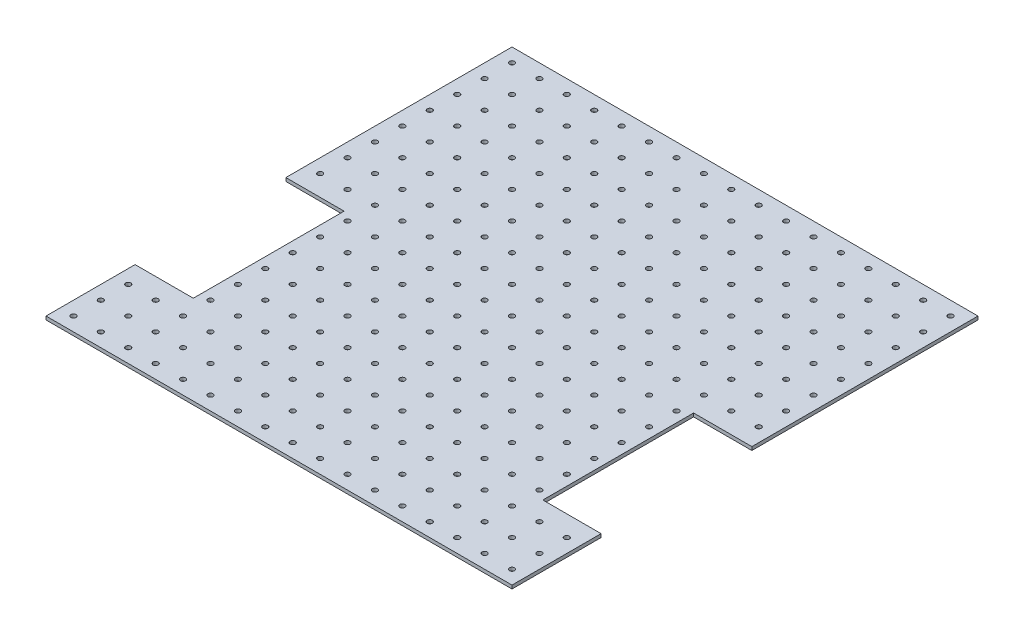
SolidWorks part; units mm, degrees
material "ABS"
ref_plane "Front Plane" through (0, 0, 0) normal (0, 0, 1) x (1, 0, 0)
ref_plane "Top Plane" through (0, 0, 0) normal (0, 1, 0) x (1, 0, 0)
ref_plane "Right Plane" through (0, 0, 0) normal (1, 0, 0) x (0, 0, -1)
sketch "Sketch1" plane through (0, 0, 0) normal (0, 1, 0) x (1, 0, 0)
  line L1 (-215.9, -215.9) -> (215.9, -215.9)
  line L2 (-215.9, -215.9) -> (-215.9, 215.9)
  line L3 (-215.9, 215.9) -> (215.9, 215.9)
  line L4 (215.9, -215.9) -> (215.9, 215.9)
  line L5 (-215.9, -215.9) -> (215.9, 215.9) construction
  line L6 (-215.9, 215.9) -> (215.9, -215.9) construction
  point P0 (0, 0)
  dimension "D1" = 431.8
  dimension "D2" = 431.8
extrude "Boss-Extrude1" add sketch "Sketch1" along normal blind 3.175
sketch "Sketch2" plane through (0, 3.175, 0) normal (0, 1, 0) x (1, 0, 0)
  line L1 (-215.9, -215.9) -> (-203.2, -215.9) construction
  line L2 (-215.9, -215.9) -> (-215.9, -203.2) construction
  line L3 (-215.9, -203.2) -> (-203.2, -203.2) construction
  line L4 (-203.2, -215.9) -> (-203.2, -203.2) construction
  circle A0 centre (-203.2, -203.2) radius 2.3813
  circle A1 centre (-177.8, -203.2) radius 2.3813
  circle A2 centre (-152.4, -203.2) radius 2.3813
  circle A3 centre (-127, -203.2) radius 2.3813
  circle A4 centre (-101.6, -203.2) radius 2.3813
  circle A5 centre (-76.2, -203.2) radius 2.3813
  circle A6 centre (-50.8, -203.2) radius 2.3812
  circle A7 centre (-25.4, -203.2) radius 2.3813
  circle A8 centre (0, -203.2) radius 2.3813
  circle A9 centre (25.4, -203.2) radius 2.3812
  circle A10 centre (50.8, -203.2) radius 2.3812
  circle A11 centre (76.2, -203.2) radius 2.3813
  circle A12 centre (101.6, -203.2) radius 2.3813
  circle A13 centre (127, -203.2) radius 2.3813
  circle A14 centre (152.4, -203.2) radius 2.3813
  circle A15 centre (177.8, -203.2) radius 2.3813
  circle A16 centre (-177.8, -177.8) radius 2.3813
  circle A17 centre (-152.4, -177.8) radius 2.3813
  circle A18 centre (-127, -177.8) radius 2.3813
  circle A19 centre (-101.6, -177.8) radius 2.3813
  circle A20 centre (-76.2, -177.8) radius 2.3813
  circle A21 centre (-50.8, -177.8) radius 2.3812
  circle A22 centre (-25.4, -177.8) radius 2.3813
  circle A23 centre (0, -177.8) radius 2.3813
  circle A24 centre (25.4, -177.8) radius 2.3812
  circle A25 centre (50.8, -177.8) radius 2.3812
  circle A26 centre (76.2, -177.8) radius 2.3813
  circle A27 centre (101.6, -177.8) radius 2.3813
  circle A28 centre (127, -177.8) radius 2.3813
  circle A29 centre (152.4, -177.8) radius 2.3813
  circle A30 centre (177.8, -177.8) radius 2.3813
  circle A31 centre (-177.8, -152.4) radius 2.3813
  circle A32 centre (-152.4, -152.4) radius 2.3813
  circle A33 centre (-127, -152.4) radius 2.3813
  circle A34 centre (-101.6, -152.4) radius 2.3813
  circle A35 centre (-76.2, -152.4) radius 2.3813
  circle A36 centre (-50.8, -152.4) radius 2.3812
  circle A37 centre (-25.4, -152.4) radius 2.3813
  circle A38 centre (0, -152.4) radius 2.3813
  circle A39 centre (25.4, -152.4) radius 2.3813
  circle A40 centre (50.8, -152.4) radius 2.3813
  circle A41 centre (76.2, -152.4) radius 2.3813
  circle A42 centre (101.6, -152.4) radius 2.3813
  circle A43 centre (127, -152.4) radius 2.3813
  circle A44 centre (152.4, -152.4) radius 2.3813
  circle A45 centre (177.8, -152.4) radius 2.3813
  circle A46 centre (-177.8, -127) radius 2.3813
  circle A47 centre (-152.4, -127) radius 2.3813
  circle A48 centre (-127, -127) radius 2.3813
  circle A49 centre (-101.6, -127) radius 2.3813
  circle A50 centre (-76.2, -127) radius 2.3813
  circle A51 centre (-50.8, -127) radius 2.3812
  circle A52 centre (-25.4, -127) radius 2.3813
  circle A53 centre (0, -127) radius 2.3813
  circle A54 centre (25.4, -127) radius 2.3812
  circle A55 centre (50.8, -127) radius 2.3812
  circle A56 centre (76.2, -127) radius 2.3813
  circle A57 centre (101.6, -127) radius 2.3813
  circle A58 centre (127, -127) radius 2.3813
  circle A59 centre (152.4, -127) radius 2.3813
  circle A60 centre (177.8, -127) radius 2.3813
  circle A61 centre (-177.8, -101.6) radius 2.3813
  circle A62 centre (-152.4, -101.6) radius 2.3813
  circle A63 centre (-127, -101.6) radius 2.3813
  circle A64 centre (-101.6, -101.6) radius 2.3813
  circle A65 centre (-76.2, -101.6) radius 2.3813
  circle A66 centre (-50.8, -101.6) radius 2.3812
  circle A67 centre (-25.4, -101.6) radius 2.3813
  circle A68 centre (0, -101.6) radius 2.3813
  circle A69 centre (25.4, -101.6) radius 2.3812
  circle A70 centre (50.8, -101.6) radius 2.3812
  circle A71 centre (76.2, -101.6) radius 2.3813
  circle A72 centre (101.6, -101.6) radius 2.3813
  circle A73 centre (127, -101.6) radius 2.3813
  circle A74 centre (152.4, -101.6) radius 2.3813
  circle A75 centre (177.8, -101.6) radius 2.3813
  circle A76 centre (-177.8, -76.2) radius 2.3813
  circle A77 centre (-152.4, -76.2) radius 2.3813
  circle A78 centre (-127, -76.2) radius 2.3813
  circle A79 centre (-101.6, -76.2) radius 2.3813
  circle A80 centre (-76.2, -76.2) radius 2.3813
  circle A81 centre (-50.8, -76.2) radius 2.3812
  circle A82 centre (-25.4, -76.2) radius 2.3813
  circle A83 centre (0, -76.2) radius 2.3813
  circle A84 centre (25.4, -76.2) radius 2.3812
  circle A85 centre (50.8, -76.2) radius 2.3813
  circle A86 centre (76.2, -76.2) radius 2.3813
  circle A87 centre (101.6, -76.2) radius 2.3813
  circle A88 centre (127, -76.2) radius 2.3813
  circle A89 centre (152.4, -76.2) radius 2.3813
  circle A90 centre (177.8, -76.2) radius 2.3813
  circle A91 centre (-177.8, -50.8) radius 2.3813
  circle A92 centre (-152.4, -50.8) radius 2.3813
  circle A93 centre (-127, -50.8) radius 2.3813
  circle A94 centre (-101.6, -50.8) radius 2.3813
  circle A95 centre (-76.2, -50.8) radius 2.3813
  circle A96 centre (-50.8, -50.8) radius 2.3812
  circle A97 centre (-25.4, -50.8) radius 2.3813
  circle A98 centre (0, -50.8) radius 2.3813
  circle A99 centre (25.4, -50.8) radius 2.3812
  circle A100 centre (50.8, -50.8) radius 2.3813
  circle A101 centre (76.2, -50.8) radius 2.3813
  circle A102 centre (101.6, -50.8) radius 2.3813
  circle A103 centre (127, -50.8) radius 2.3813
  circle A104 centre (152.4, -50.8) radius 2.3813
  circle A105 centre (177.8, -50.8) radius 2.3813
  circle A106 centre (-177.8, -25.4) radius 2.3813
  circle A107 centre (-152.4, -25.4) radius 2.3813
  circle A108 centre (-127, -25.4) radius 2.3813
  circle A109 centre (-101.6, -25.4) radius 2.3813
  circle A110 centre (-76.2, -25.4) radius 2.3813
  circle A111 centre (-50.8, -25.4) radius 2.3812
  circle A112 centre (-25.4, -25.4) radius 2.3813
  circle A113 centre (0, -25.4) radius 2.3813
  circle A114 centre (25.4, -25.4) radius 2.3812
  circle A115 centre (50.8, -25.4) radius 2.3812
  circle A116 centre (76.2, -25.4) radius 2.3813
  circle A117 centre (101.6, -25.4) radius 2.3813
  circle A118 centre (127, -25.4) radius 2.3813
  circle A119 centre (152.4, -25.4) radius 2.3813
  circle A120 centre (177.8, -25.4) radius 2.3813
  circle A121 centre (-177.8, 0) radius 2.3813
  circle A122 centre (-152.4, 0) radius 2.3813
  circle A123 centre (-127, 0) radius 2.3813
  circle A124 centre (-101.6, 0) radius 2.3813
  circle A125 centre (-76.2, 0) radius 2.3813
  circle A126 centre (-50.8, 0) radius 2.3812
  circle A127 centre (-25.4, 0) radius 2.3813
  circle A128 centre (0, 0) radius 2.3813
  circle A129 centre (25.4, 0) radius 2.3812
  circle A130 centre (50.8, 0) radius 2.3812
  circle A131 centre (76.2, 0) radius 2.3813
  circle A132 centre (101.6, 0) radius 2.3813
  circle A133 centre (127, 0) radius 2.3813
  circle A134 centre (152.4, 0) radius 2.3813
  circle A135 centre (177.8, 0) radius 2.3813
  circle A136 centre (-177.8, 25.4) radius 2.3813
  circle A137 centre (-152.4, 25.4) radius 2.3813
  circle A138 centre (-127, 25.4) radius 2.3813
  circle A139 centre (-101.6, 25.4) radius 2.3813
  circle A140 centre (-76.2, 25.4) radius 2.3813
  circle A141 centre (-50.8, 25.4) radius 2.3812
  circle A142 centre (-25.4, 25.4) radius 2.3813
  circle A143 centre (0, 25.4) radius 2.3813
  circle A144 centre (25.4, 25.4) radius 2.3812
  circle A145 centre (50.8, 25.4) radius 2.3812
  circle A146 centre (76.2, 25.4) radius 2.3813
  circle A147 centre (101.6, 25.4) radius 2.3813
  circle A148 centre (127, 25.4) radius 2.3813
  circle A149 centre (152.4, 25.4) radius 2.3813
  circle A150 centre (177.8, 25.4) radius 2.3813
  circle A151 centre (-177.8, 50.8) radius 2.3813
  circle A152 centre (-152.4, 50.8) radius 2.3813
  circle A153 centre (-127, 50.8) radius 2.3813
  circle A154 centre (-101.6, 50.8) radius 2.3813
  circle A155 centre (-76.2, 50.8) radius 2.3813
  circle A156 centre (-50.8, 50.8) radius 2.3812
  circle A157 centre (-25.4, 50.8) radius 2.3813
  circle A158 centre (0, 50.8) radius 2.3813
  circle A159 centre (25.4, 50.8) radius 2.3812
  circle A160 centre (50.8, 50.8) radius 2.3812
  circle A161 centre (76.2, 50.8) radius 2.3813
  circle A162 centre (101.6, 50.8) radius 2.3813
  circle A163 centre (127, 50.8) radius 2.3813
  circle A164 centre (152.4, 50.8) radius 2.3813
  circle A165 centre (177.8, 50.8) radius 2.3813
  circle A166 centre (-177.8, 76.2) radius 2.3813
  circle A167 centre (-152.4, 76.2) radius 2.3813
  circle A168 centre (-127, 76.2) radius 2.3813
  circle A169 centre (-101.6, 76.2) radius 2.3813
  circle A170 centre (-76.2, 76.2) radius 2.3813
  circle A171 centre (-50.8, 76.2) radius 2.3812
  circle A172 centre (-25.4, 76.2) radius 2.3813
  circle A173 centre (0, 76.2) radius 2.3813
  circle A174 centre (25.4, 76.2) radius 2.3812
  circle A175 centre (50.8, 76.2) radius 2.3812
  circle A176 centre (76.2, 76.2) radius 2.3813
  circle A177 centre (101.6, 76.2) radius 2.3813
  circle A178 centre (127, 76.2) radius 2.3813
  circle A179 centre (152.4, 76.2) radius 2.3813
  circle A180 centre (177.8, 76.2) radius 2.3813
  circle A181 centre (-177.8, 101.6) radius 2.3813
  circle A182 centre (-152.4, 101.6) radius 2.3813
  circle A183 centre (-127, 101.6) radius 2.3813
  circle A184 centre (-101.6, 101.6) radius 2.3813
  circle A185 centre (-76.2, 101.6) radius 2.3813
  circle A186 centre (-50.8, 101.6) radius 2.3812
  circle A187 centre (-25.4, 101.6) radius 2.3813
  circle A188 centre (0, 101.6) radius 2.3813
  circle A189 centre (25.4, 101.6) radius 2.3812
  circle A190 centre (50.8, 101.6) radius 2.3812
  circle A191 centre (76.2, 101.6) radius 2.3813
  circle A192 centre (101.6, 101.6) radius 2.3813
  circle A193 centre (127, 101.6) radius 2.3813
  circle A194 centre (152.4, 101.6) radius 2.3813
  circle A195 centre (177.8, 101.6) radius 2.3813
  circle A196 centre (-177.8, 127) radius 2.3813
  circle A197 centre (-152.4, 127) radius 2.3813
  circle A198 centre (-127, 127) radius 2.3813
  circle A199 centre (-101.6, 127) radius 2.3813
  circle A200 centre (-76.2, 127) radius 2.3813
  circle A201 centre (-50.8, 127) radius 2.3812
  circle A202 centre (-25.4, 127) radius 2.3813
  circle A203 centre (0, 127) radius 2.3813
  circle A204 centre (25.4, 127) radius 2.3812
  circle A205 centre (50.8, 127) radius 2.3812
  circle A206 centre (76.2, 127) radius 2.3813
  circle A207 centre (101.6, 127) radius 2.3813
  circle A208 centre (127, 127) radius 2.3813
  circle A209 centre (152.4, 127) radius 2.3813
  circle A210 centre (177.8, 127) radius 2.3813
  circle A211 centre (-177.8, 152.4) radius 2.3813
  circle A212 centre (-152.4, 152.4) radius 2.3813
  circle A213 centre (-127, 152.4) radius 2.3813
  circle A214 centre (-101.6, 152.4) radius 2.3813
  circle A215 centre (-76.2, 152.4) radius 2.3813
  circle A216 centre (-50.8, 152.4) radius 2.3812
  circle A217 centre (-25.4, 152.4) radius 2.3813
  circle A218 centre (0, 152.4) radius 2.3813
  circle A219 centre (25.4, 152.4) radius 2.3812
  circle A220 centre (50.8, 152.4) radius 2.3812
  circle A221 centre (76.2, 152.4) radius 2.3813
  circle A222 centre (101.6, 152.4) radius 2.3813
  circle A223 centre (127, 152.4) radius 2.3813
  circle A224 centre (152.4, 152.4) radius 2.3813
  circle A225 centre (177.8, 152.4) radius 2.3813
  circle A226 centre (-177.8, 177.8) radius 2.3813
  circle A227 centre (-152.4, 177.8) radius 2.3813
  circle A228 centre (-127, 177.8) radius 2.3813
  circle A229 centre (-101.6, 177.8) radius 2.3813
  circle A230 centre (-76.2, 177.8) radius 2.3813
  circle A231 centre (-50.8, 177.8) radius 2.3812
  circle A232 centre (-25.4, 177.8) radius 2.3813
  circle A233 centre (0, 177.8) radius 2.3813
  circle A234 centre (25.4, 177.8) radius 2.3812
  circle A235 centre (50.8, 177.8) radius 2.3812
  circle A236 centre (76.2, 177.8) radius 2.3813
  circle A237 centre (101.6, 177.8) radius 2.3813
  circle A238 centre (127, 177.8) radius 2.3813
  circle A239 centre (152.4, 177.8) radius 2.3813
  circle A240 centre (177.8, 177.8) radius 2.3813
  circle A241 centre (-203.2, -177.8) radius 2.3813
  circle A242 centre (-203.2, -152.4) radius 2.3813
  circle A243 centre (-203.2, -127) radius 2.3813
  circle A244 centre (-203.2, -101.6) radius 2.3813
  circle A245 centre (-203.2, -76.2) radius 2.3813
  circle A246 centre (-203.2, -50.8) radius 2.3813
  circle A247 centre (-203.2, -25.4) radius 2.3813
  circle A248 centre (-203.2, 0) radius 2.3813
  circle A249 centre (-203.2, 25.4) radius 2.3813
  circle A250 centre (-203.2, 50.8) radius 2.3813
  circle A251 centre (-203.2, 76.2) radius 2.3813
  circle A252 centre (-203.2, 101.6) radius 2.3813
  circle A253 centre (-203.2, 127) radius 2.3813
  circle A254 centre (-203.2, 152.4) radius 2.3813
  circle A255 centre (-203.2, 177.8) radius 2.3813
  circle A256 centre (203.2, -203.2) radius 2.3813
  circle A257 centre (203.2, -177.8) radius 2.3813
  circle A258 centre (203.2, -152.4) radius 2.3813
  circle A259 centre (203.2, -127) radius 2.3813
  circle A260 centre (203.2, -101.6) radius 2.3813
  circle A261 centre (203.2, -76.2) radius 2.3813
  circle A262 centre (203.2, -50.8) radius 2.3813
  circle A263 centre (203.2, -25.4) radius 2.3813
  circle A264 centre (203.2, 0) radius 2.3813
  circle A265 centre (203.2, 25.4) radius 2.3813
  circle A266 centre (203.2, 50.8) radius 2.3813
  circle A267 centre (203.2, 76.2) radius 2.3813
  circle A268 centre (203.2, 101.6) radius 2.3813
  circle A269 centre (203.2, 127) radius 2.3813
  circle A270 centre (203.2, 152.4) radius 2.3813
  circle A271 centre (203.2, 177.8) radius 2.3813
  circle A272 centre (-203.2, 203.2) radius 2.3813
  circle A273 centre (-177.8, 203.2) radius 2.3813
  circle A274 centre (-152.4, 203.2) radius 2.3813
  circle A275 centre (-127, 203.2) radius 2.3813
  circle A276 centre (-101.6, 203.2) radius 2.3813
  circle A277 centre (-76.2, 203.2) radius 2.3813
  circle A278 centre (-50.8, 203.2) radius 2.3813
  circle A279 centre (-25.4, 203.2) radius 2.3813
  circle A280 centre (0, 203.2) radius 2.3813
  circle A281 centre (25.4, 203.2) radius 2.3813
  circle A282 centre (50.8, 203.2) radius 2.3813
  circle A283 centre (76.2, 203.2) radius 2.3813
  circle A284 centre (101.6, 203.2) radius 2.3813
  circle A285 centre (127, 203.2) radius 2.3813
  circle A286 centre (152.4, 203.2) radius 2.3813
  circle A287 centre (177.8, 203.2) radius 2.3813
  circle A288 centre (203.2, 203.2) radius 2.3813
  dimension "D3" = 17
  dimension "D1" = 12.7
  dimension "D2" = 12.7
  dimension "D4" = 17
extrude "Cut-Extrude1" cut sketch "Sketch2" against normal blind 3.175
sketch "Sketch3" plane through (0, 3.175, 0) normal (0, 1, 0) x (1, 0, 0)
  line L0 (-215.9, 215.9) -> (-215.9, -215.9) construction
  line L14 (-269.875, -133.35) -> (-161.925, -133.35)
  line L15 (-215.9, -215.9) -> (-215.9, -63.5) construction
  line L16 (-269.875, -133.35) -> (-269.875, 6.35)
  line L17 (-269.875, 6.35) -> (-161.925, 6.35)
  line L18 (-161.925, -133.35) -> (-161.925, 6.35)
  line L19 (-269.875, -133.35) -> (-161.925, 6.35) construction
  line L20 (-269.875, 6.35) -> (-161.925, -133.35) construction
  dimension "D1" = 107.95
  dimension "D2" = 139.7
extrude "Cut-Extrude2" cut sketch "Sketch3" against normal through all
mirror "Mirror1" about plane through (0, 0, 0) normal (1, 0, 0) of "Cut-Extrude2"
